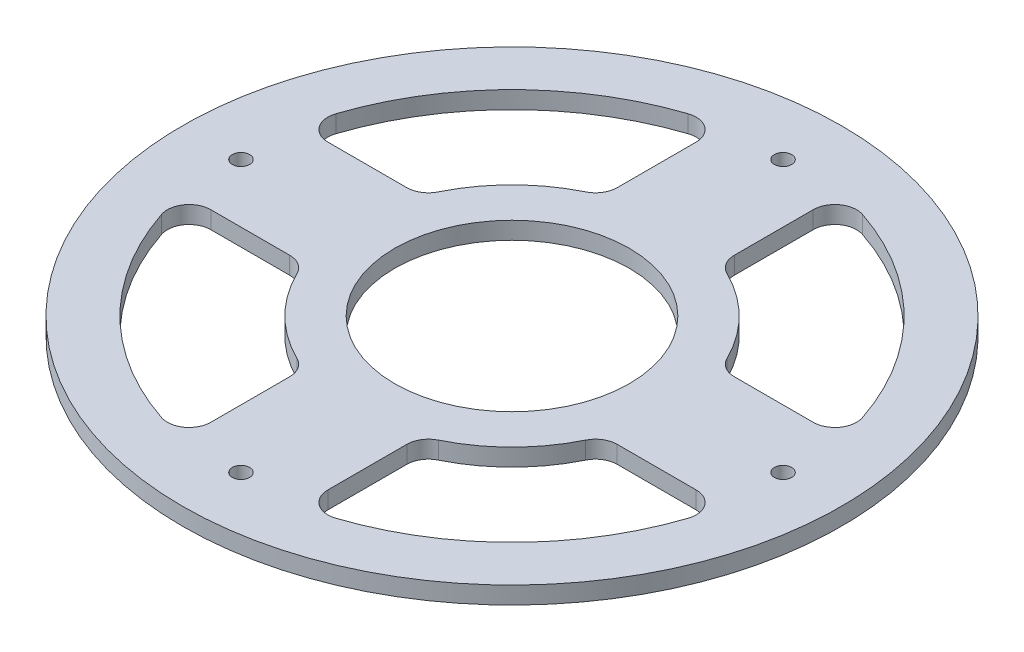
SolidWorks part; units mm, degrees
material "Custom Plastic"
ref_plane "Front Plane" through (0, 0, 0) normal (0, 0, 1) x (1, 0, 0)
ref_plane "Top Plane" through (0, 0, 0) normal (0, 1, 0) x (1, 0, 0)
ref_plane "Right Plane" through (0, 0, 0) normal (1, 0, 0) x (0, 0, -1)
sketch "Sketch1" plane through (0, 0, 0) normal (0, 1, 0) x (1, 0, 0)
  circle A0 centre (0, 0) radius 76
  circle A1 centre (0, 0) radius 27.051
  circle A2 centre (0, 0) radius 62.5 construction
  circle A3 centre (0, 62.5) radius 2
  circle A4 centre (62.5, 0) radius 2
  circle A5 centre (0, -62.5) radius 2
  circle A6 centre (-62.5, 0) radius 2
  dimension "D1" = 152
  dimension "D2" = 54.102
  dimension "D3" = 125
  dimension "D4" = 4
extrude "Boss-Extrude1" add sketch "Sketch1" along normal blind 2 and the other way blind 2
sketch "Sketch3" plane through (0, -2, 0) normal (0, -1, 0) x (1, 0, 0)
  circle A0 centre (0, 0) radius 27.051
sketch "Sketch4" plane through (0, 2, 0) normal (0, 1, 0) x (1, 0, 0)
  line L0 (134.0846, 0) -> (0, 0) construction
  line L1 (0, 0) -> (0, 97.8812) construction
  line L2 (13.5, 62.5) -> (13.5, 34.504)
  line L3 (34.504, 13.5) -> (62.5, 13.5)
  line L4 (-34.504, 13.5) -> (-62.5, 13.5)
  line L5 (-13.5, 62.5) -> (-13.5, 34.504)
  line L6 (34.504, -13.5) -> (62.5, -13.5)
  line L7 (13.5, -62.5) -> (13.5, -34.504)
  line L8 (-13.5, -62.5) -> (-13.5, -34.504)
  line L9 (-34.504, -13.5) -> (-62.5, -13.5)
  arc A0 (13.5, 62.5) -> (62.5, 13.5) centre (0, 0) cw
  arc A7 (-13.5, 62.5) -> (-62.5, 13.5) centre (0, 0) ccw
  arc A8 (13.5, -62.5) -> (62.5, -13.5) centre (0, 0) ccw
  arc A10 (-13.5, -62.5) -> (-62.5, -13.5) centre (0, 0) cw
  circle A11 centre (0, 0) radius 37.051
  circle A12 centre (0, 0) radius 27.051 construction
  dimension "D1" = 10
  dimension "D4" = 63.9414
  dimension "D2" = 27
  dimension "D3" = 27
extrude "Cut-Extrude2" cut sketch "Sketch4" against normal through all contours A11 L5 A7 L4 | A11 L3 A0 L2 | A11 L7 A8 L6 | A11 L9 A10 L8 region at (35.3253, 2, -35.3253) region at (-35.3253, 2, -35.3253) region at (35.3253, 2, 35.3253) region at (-35.3253, 2, 35.3253)
fillet "Fillet1" radius 5 16 edges at (-13.5, 0, 34.504) (-13.5, 0, 62.5) (-34.504, 0, 13.5) (-62.5, 0, 13.5) (13.5, 0, 62.5) (13.5, 0, 34.504) (34.504, 0, 13.5) (62.5, 0, 13.5) (34.504, 0, -13.5) (13.5, 0, -34.504) (62.5, 0, -13.5) (13.5, 0, -62.5) (-62.5, 0, -13.5) (-34.504, 0, -13.5) (-13.5, 0, -34.504) (-13.5, 0, -62.5)
